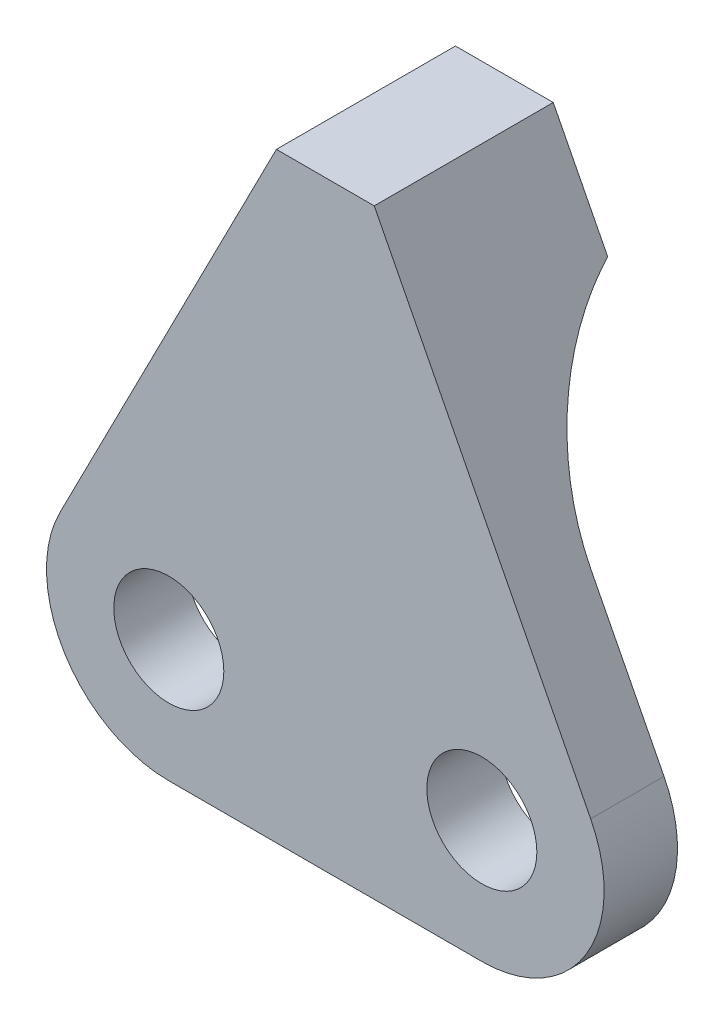
SolidWorks part; units mm, degrees
material "PET"
ref_plane "Front Plane" through (0, 0, 0) normal (0, 0, 1) x (1, 0, 0)
ref_plane "Top Plane" through (0, 0, 0) normal (0, 1, 0) x (1, 0, 0)
ref_plane "Right Plane" through (0, 0, 0) normal (1, 0, 0) x (0, 0, -1)
sketch "Sketch1" plane through (0, 0, 0) normal (0, 0, 1) x (1, 0, 0)
  line L0 (10.16, 24.1544) -> (10.16, -24.1544) construction
  line L1 (28.2575, 24.1544) -> (-7.9375, 24.1544) construction
  line L2 (-7.9375, -24.1544) -> (28.2575, -24.1544) construction
  line L3 (0, -7.9375) -> (20.32, -7.9375)
  line L4 (13.335, 31.0505) -> (6.985, 31.0505)
  line L5 (13.335, 31.0505) -> (27.3848, 3.6183)
  line L7 (10.795, 28.5105) -> (9.525, 28.5105) construction
  line L14 (6.985, 31.0505) -> (-7.0648, 3.6183)
  circle A0 centre (0, 0) radius 7.9375 construction
  arc A1 (27.3848, 3.6183) -> (20.32, -7.9375) centre (20.32, 0) cw
  circle A2 centre (0, 0) radius 7.9375
  arc A3 (-7.0648, 3.6183) -> (0, -7.9375) centre (0, 0) ccw
  point P10 (10.16, -7.9375)
  point P22 (10.16, 31.0505)
  dimension "D2" = 2.54
  dimension "D3" = 3.175
  dimension "D1" = 0
extrude "Boss-Extrude1" add sketch "Sketch1" along normal blind 4.7625
hole_wizard "1/4 Clearance Hole1" positions "Sketch4" profile "Sketch5" hole size "1/4" standard "ANSI Inch" end condition through all
sketch "Sketch4" plane through (0, 0, 4.7625) normal (0, 0, 1) x (1, 0, 0)
  circle A0 centre (0, 0) radius 3.5712 construction
  circle A1 centre (20.32, 0) radius 3.5712 construction
  point P0 (0, 0)
  point P2 (20.32, 0)
sketch "Sketch5" plane through (0, 0, 4.7625) normal (1, 0, 0) x (0, -1, 0)
  line L0 (0, 0) -> (0, 4.7625)
  line L1 (0, 4.7625) -> (3.5712, 4.7625)
  line L2 (3.5712, 4.7625) -> (3.5712, 0)
  line L5 (3.5712, 0) -> (0, 0)
  line L11 (0, -6.35) -> (0, 107.95) construction
  dimension "Thru Hole Dia." = 7.1425
  dimension "Thru Hole Depth" = 4.7625
sketch "Sketch6" plane through (0, 0, 0) normal (0, 0, -1) x (-1, 0, 0)
  line L0 (-16.8669, 24.1544) -> (-3.4531, 24.1544)
  line L1 (-28.2575, 24.1544) -> (7.9375, 24.1544) construction
  line L4 (7.0648, 3.6183) -> (-6.985, 31.0505)
  line L5 (-6.985, 31.0505) -> (-13.335, 31.0505)
  line L6 (-13.335, 31.0505) -> (-27.3848, 3.6183)
  line L7 (-20.32, -7.9375) -> (0, -7.9375)
  line L8 (-3.4531, 24.1544) -> (-6.985, 31.0505)
  line L9 (-6.985, 31.0505) -> (-13.335, 31.0505)
  line L10 (-13.335, 31.0505) -> (-16.8669, 24.1544)
  arc A2 (0, -7.9375) -> (7.0648, 3.6183) centre (0, 0) ccw
  arc A3 (-27.3848, 3.6183) -> (-20.32, -7.9375) centre (-20.32, 0) ccw
  dimension "D1" = 0
extrude "Boss-Extrude2" add sketch "Sketch6" along normal blind 6.858
draft "Draft1" type of draft neutral plane draft angle 30 faces to draft 1 face at (10.16, 24.1544, -3.429) neutral plane through (0, 0, -6.858) neutral plane normal (0, 0, -1) parameters "D1"=30
fillet "Fillet1" radius 12.7 1 edges at (10.16, 20.195, 0)
